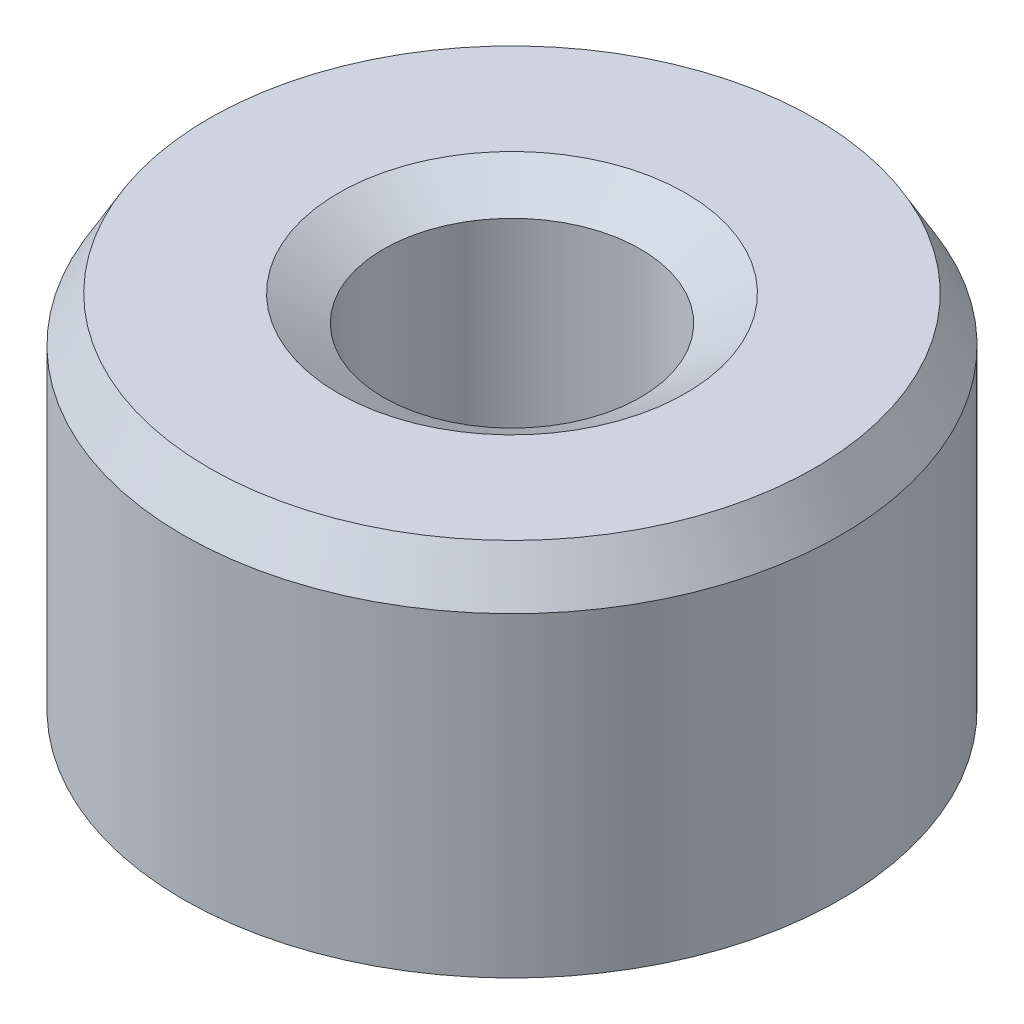
SolidWorks part; units mm, degrees
ref_plane "Front Plane" through (0, 0, 0) normal (0, 0, 1) x (1, 0, 0)
ref_plane "Top Plane" through (0, 0, 0) normal (0, 1, 0) x (1, 0, 0)
ref_plane "Right Plane" through (0, 0, 0) normal (1, 0, 0) x (0, 0, -1)
sketch "Sketch1" plane through (0, 0, 0) normal (0, 1, 0) x (1, 0, 0)
  circle A0 centre (0, 0) radius 27.5
  dimension "SLEEVE_OD" = 55
extrude "Boss-Extrude1" add sketch "Sketch1" along normal blind 32.3263
sketch "Sketch2" plane through (0, 0, 0) normal (0, 1, 0) x (1, 0, 0)
  circle A0 centre (0, 0) radius 10.7461
  dimension "BORE_D" = 21.4922
extrude "Cut-Extrude1" cut sketch "Sketch2" along normal through all
chamfer "Chamfer1" distance 3.7684 angle 30 4 edges at (0, 32.3263, 10.7461) (0, 0, 10.7461) (0, 0, 27.5) (0, 32.3263, 27.5) first distance on face at (0, 32.3263, 10.7461) first distance on face at (0, 0, 10.7461) first distance on face at (0, 32.3263, 27.5)
